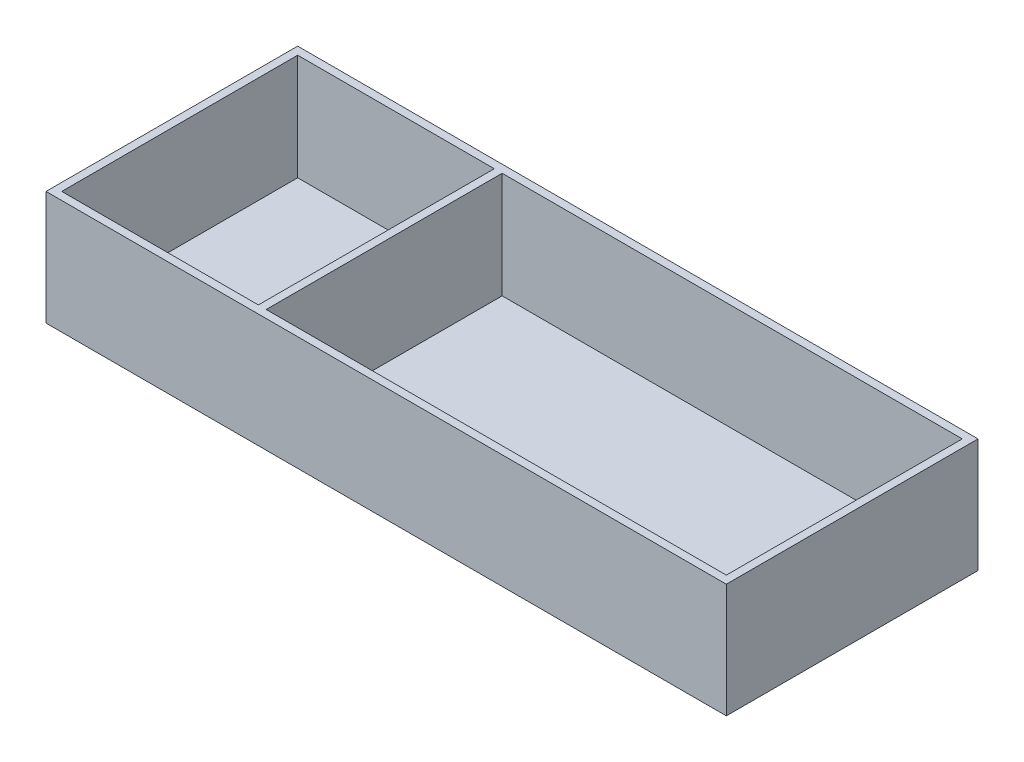
SolidWorks part; units mm, degrees
ref_plane "Front" through (0, 0, 0) normal (0, 0, 1) x (1, 0, 0)
ref_plane "Top" through (0, 0, 0) normal (0, 1, 0) x (1, 0, 0)
ref_plane "Right" through (0, 0, 0) normal (1, 0, 0) x (0, 0, -1)
sketch "Sketch1" plane through (0, 0, 0) normal (0, 1, 0) x (1, 0, 0)
  line L1 (-86.5, -32) -> (86.5, -32)
  line L2 (-86.5, -32) -> (-86.5, 32)
  line L3 (-86.5, 32) -> (86.5, 32)
  line L4 (86.5, -32) -> (86.5, 32)
  line L5 (-86.5, -32) -> (86.5, 32) construction
  line L6 (-86.5, 32) -> (86.5, -32) construction
  point P0 (0, 0)
  dimension "D1" = 64
  dimension "D2" = 173
extrude "Boss-Extrude1" add sketch "Sketch1" along normal blind 29
shell "Shell1" thickness 2 removed face at (0, 29, 0)
sketch "Sketch3" plane through (0, 2, 0) normal (0, 1, 0) x (1, 0, 0)
  line L0 (84.5, 30) -> (-84.5, 30) construction
  line L1 (-34.5, -30) -> (-32.5, -30)
  line L2 (-34.5, -30) -> (-34.5, 30)
  line L3 (-34.5, 30) -> (-32.5, 30)
  line L4 (-32.5, -30) -> (-32.5, 30)
  line L5 (-34.5, -30) -> (-32.5, 30) construction
  line L6 (-34.5, 30) -> (-32.5, -30) construction
  line L8 (84.5, -30) -> (84.5, 30) construction
  point P0 (-33.5, 0)
  dimension "D1" = 2
  dimension "D2" = 117
extrude "Boss-Extrude2" add sketch "Sketch3" along normal up to vertex (27 mm away) up to point (84.5, 29, -30)
